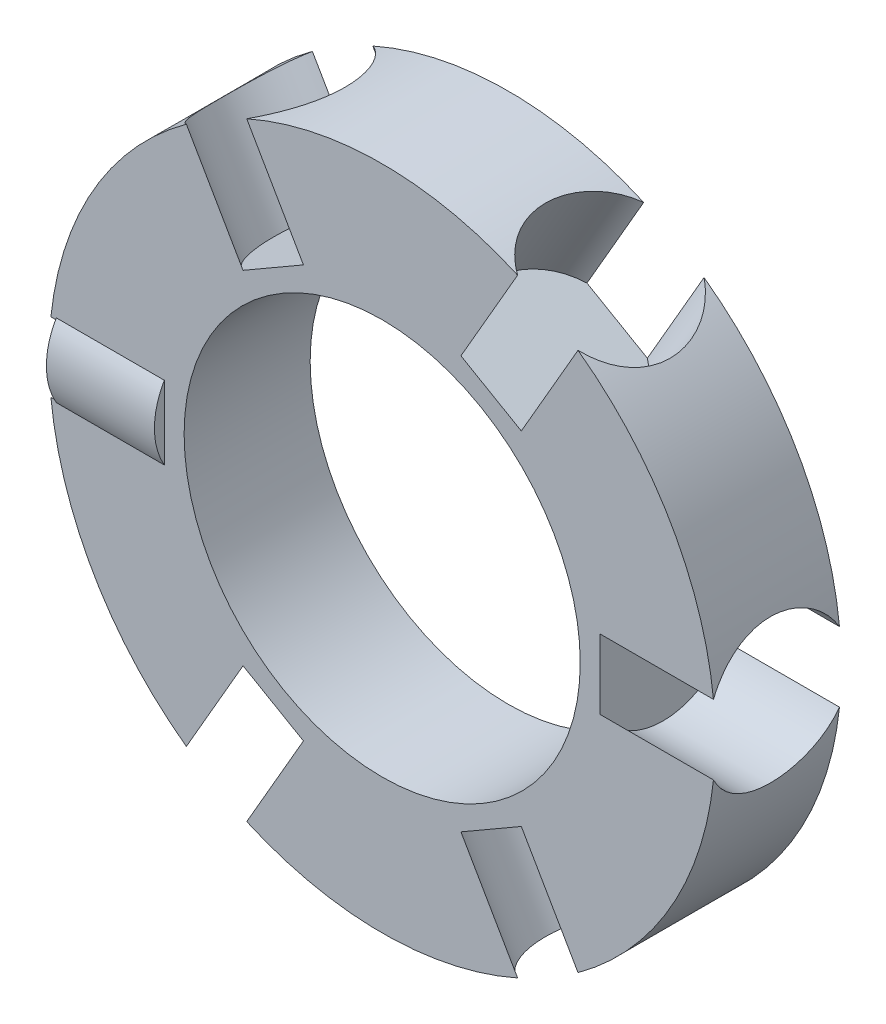
SolidWorks part; units mm, degrees
ref_plane "Top Plane" through (0, 0, 0) normal (0, 0, 1) x (1, 0, 0)
ref_plane "Right Plane" through (0, 0, 0) normal (0, 1, 0) x (1, 0, 0)
ref_plane "Front Plane" through (0, 0, 0) normal (1, 0, 0) x (0, 0, -1)
ref_axis "x-axis" through (-88.99, 0, 0) along (1, 0, 0)
ref_axis "y-axis" through (0, -55, 0) along (0, 1, 0)
ref_axis "z-axis" through (0, 0, 55) along (0, 0, -1)
sketch "Sketch1" plane through (0, 0, 0) normal (0, 0, 1) x (1, 0, 0)
  line L8 (-19.9785, 0) -> (0, 0) construction
  line L16 (0, 0) -> (0, -20.7846) construction
  line L23 (0, 0) -> (0, -20.7846) construction
  circle A0 centre (0, 0) radius 11
  circle A3 centre (0, 0) radius 18.5
  dimension "D1" = 22
  dimension "D2" = 37
extrude "Boss-Extrude1" add sketch "Sketch1" along normal mid plane 7
ref_plane "Plane1" through (-18.5, 0, 0) normal (-1, 0, 0) x (0, 0, 1)
sketch "Sketch2" plane through (-18.5, -17.1931, 0) normal (1, 0, 0) x (0, -1, 0)
  circle A0 centre (-17.1931, 0) radius 4
  dimension "D1" = 8
extrude "Cut-Extrude3" cut sketch "Sketch2" along normal blind 6.4
pattern_circular "CirPattern1" count 6 over 360 about axis through (0, 0, 3.5) along (0, 0, 1) of "Cut-Extrude3"
sketch "Sketch3" plane through (-12.1, 0, 0) normal (-1, 0, 0) x (0, -1, 0)
  circle A0 centre (0, 0) radius 4.05
  dimension "D1" = 4.05
extrude "Boss-Extrude2" add sketch "Sketch3" along normal blind 6
